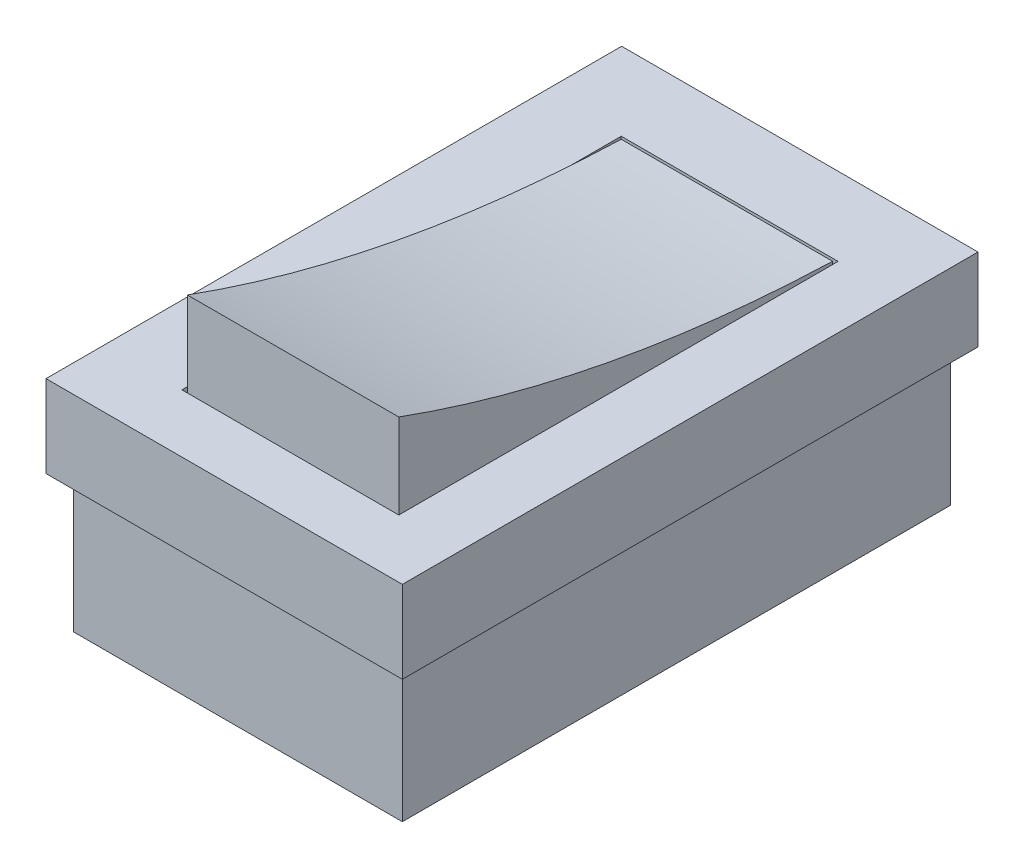
SolidWorks part; units mm, degrees
material "ABS"
ref_plane "Front Plane" through (0, 0, 0) normal (0, 0, 1) x (1, 0, 0)
ref_plane "Top Plane" through (0, 0, 0) normal (0, 1, 0) x (1, 0, 0)
ref_plane "Right Plane" through (0, 0, 0) normal (1, 0, 0) x (0, 0, -1)
sketch "Sketch2" plane through (0, 0, 0) normal (0, 1, 0) x (1, 0, 0)
  line L0 (6.2318, 10.9023) -> (-6.7682, 10.9023)
  line L1 (5.7318, 10.4023) -> (-6.2682, 10.4023)
  line L2 (5.7318, 10.4023) -> (5.7318, -9.5977)
  line L3 (5.7318, -9.5977) -> (-6.2682, -9.5977)
  line L4 (-6.2682, 10.4023) -> (-6.2682, -9.5977)
  line L5 (5.7318, 10.4023) -> (-6.2682, -9.5977) construction
  line L6 (5.7318, -9.5977) -> (-6.2682, 10.4023) construction
  line L7 (-6.7682, 10.9023) -> (-6.7682, -10.0977)
  line L8 (6.2318, -10.0977) -> (-6.7682, -10.0977)
  line L9 (6.2318, 10.9023) -> (6.2318, -10.0977)
  point P0 (-0.2682, 0.4023)
  dimension "D1" = 0.5
extrude "Boss-Extrude1" add sketch "Sketch2" along normal blind 3
extrude "Boss-Extrude2" add sketch "Sketch2<2>" along normal blind 3 and the other way blind 5 contours L1 L4 L3 L2 region at (-0.2682, 0, -0.4023)
sketch "Sketch2<2>" plane through (0, 0, 0) normal (0, 1, 0) x (1, 0, 0) same geometry as "Sketch2"
sketch "Sketch3" plane through (0, 3, 0) normal (0, 1, 0) x (1, 0, 0)
  line L0 (3.9767, 8.053) -> (-3.9334, 8.053)
  line L1 (3.8767, 7.953) -> (-3.8334, 7.953)
  line L2 (3.8767, 7.953) -> (3.8767, -7.873)
  line L3 (3.8767, -7.873) -> (-3.8334, -7.873)
  line L4 (-3.8334, 7.953) -> (-3.8334, -7.873)
  line L5 (3.8767, 7.953) -> (-3.8334, -7.873) construction
  line L6 (3.8767, -7.873) -> (-3.8334, 7.953) construction
  line L7 (-3.9334, 8.053) -> (-3.9334, -7.973)
  line L8 (3.9767, -7.973) -> (-3.9334, -7.973)
  line L9 (3.9767, 8.053) -> (3.9767, -7.973)
  point P0 (0.0217, 0.04)
  dimension "D1" = 0.1
extrude "Cut-Extrude1" cut sketch "Sketch3" against normal blind 3
extrude "Boss-Extrude3" add sketch "Sketch3<2>" along normal blind 3 contours L1 L4 L3 L2 region at (0.0217, 3, -0.04)
sketch "Sketch3<2>" plane through (0, 3, 0) normal (0, 1, 0) x (1, 0, 0) same geometry as "Sketch3"
sketch "Sketch5" plane through (3.8767, 0, 0) normal (1, 0, 0) x (0, 0, -1)
  line L2 (7.9806, 3.0028) -> (-0.5161, 3.2903) construction
  line L4 (-0.5161, 3.2903) -> (-8.0123, 6.0485) construction
  spline S0 degree 2 poles (7.9806, 3.0028) (-0.5161, 3.2903) (-8.0123, 6.0485) knots 0 0 0 1 1 1
  point P1 (-0.532, 5.9946)
  point P2 (-0.5656, 3.0501)
  point P3 (0, 0)
  point P4 (7.9529, 3)
  point P6 (-7.8792, 5.9686)
  point P7 (-0.5161, 3.2903)
  point P9 (7.9806, 3.0028)
  point P10 (-7.912, 6.0524)
  point P11 (-8.0123, 6.0485)
  line M2 (7.953, 0) -> (7.953, 6)
  line M3 (7.953, 6) -> (-7.873, 6)
  line M4 (-7.873, 6) -> (-7.873, 0)
extrude "Cut-Extrude2" cut sketch "Sketch5" against normal through all contours S0 M2 M3 M4 region at (3.8767, 4.8347, -2.0605)
